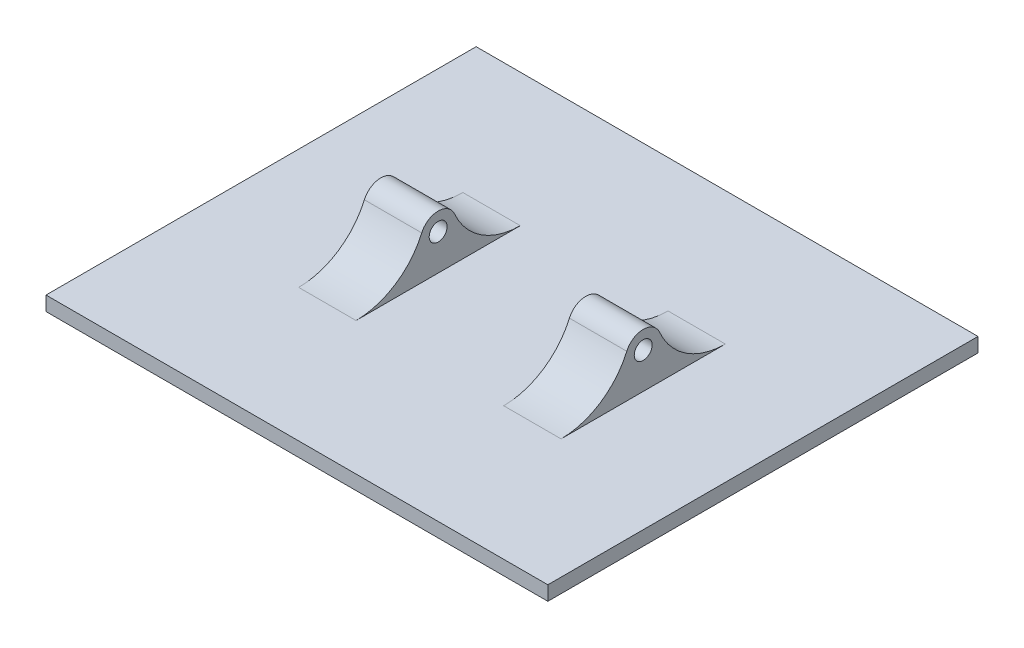
SolidWorks part; units mm, degrees
ref_plane "Front" through (0, 0, 0) normal (0, 0, 1) x (1, 0, 0)
ref_plane "Top" through (0, 0, 0) normal (0, 1, 0) x (1, 0, 0)
ref_plane "Right" through (0, 0, 0) normal (1, 0, 0) x (0, 0, -1)
sketch "Sketch1" plane through (0, 0, 0) normal (0, 0, 1) x (1, 0, 0)
  line L1 (0, 0) -> (20, 0)
  line L2 (0, 0) -> (0, 60)
  line L3 (0, 60) -> (20, 60)
  line L4 (20, 0) -> (20, 60)
  dimension "D1" = 60
  dimension "D2" = 20
extrude "Boss-Extrude1" add sketch "Sketch1" along normal blind 5
sketch "Sketch2" plane through (20, 0, 0) normal (1, 0, 0) x (0, 0, -1)
  line L0 (-5, 60) -> (0, 60) construction
  circle A0 centre (-2.5, 60) radius 2.5
  circle A1 centre (-2.5, 60) radius 1.25
  dimension "D1" = 2.5
extrude "Boss-Extrude2" add sketch "Sketch2" against normal up to surface (20 mm away) up to face at (0, 30, 2.5)
sketch "Sketch3" plane through (0, 0, 0) normal (-1, 0, 0) x (0, 0, 1)
  line L0 (3.75, 60) -> (1.25, 60) construction
  circle A0 centre (2.5, 60) radius 1.25
extrude "Cut-Extrude1" cut sketch "Sketch3" against normal blind 29
sketch "Sketch4" plane through (0, 0, 0) normal (-1, 0, 0) x (0, 0, 1)
  line L0 (5, 0) -> (0, 0) construction
  circle A0 centre (2.5, 0) radius 2.5
  circle A1 centre (2.5, 0) radius 1.25
  dimension "D1" = 2.5
extrude "Boss-Extrude3" add sketch "Sketch4" against normal up to surface (20 mm away) up to face at (20, 30.625, 2.5)
sketch "Sketch5" plane through (20, 0, 0) normal (1, 0, 0) x (0, 0, -1)
  line L0 (-3.75, 0) -> (-1.25, 0) construction
  circle A0 centre (-2.5, 0) radius 1.25
extrude "Cut-Extrude2" cut sketch "Sketch5" against normal blind 29
sketch "Sketch7" plane through (0, 0, 0) normal (-1, 0, 0) x (0, 0, 1)
  line L0 (0, -5) -> (-27.5, -5)
  line L2 (0, 0) -> (0, -5)
  line L4 (5, 0) -> (5, -5)
  line L5 (5, -5) -> (32.5, -5)
  line L6 (32.5, -5) -> (5, -5)
  line L7 (32.5, -5) -> (32.5, -7)
  line L8 (32.5, -5) -> (32.5, -7)
  line L9 (32.5, -7) -> (-27.5, -7)
  line L10 (-27.5, -5) -> (-27.5, -7)
  circle A0 centre (2.5, 0) radius 1.25
  arc A1 (5, 0) -> (0, 0) centre (2.5, 0) ccw
  point P13 (2.5, -7)
  point P14 (0, 0)
  arc M8 (0, 0) -> (5, 0) centre (2.5, 0) ccw
  circle M12 centre (2.5, 0) radius 1.25
  dimension "D1" = 5
  dimension "D2" = 2
  dimension "D3" = 60
extrude "Boss-Extrude4" add sketch "Sketch7" along normal blind 70 contours L0 L10 L9 L7 L5 L4 L2 M8 | A1 M8 M12 region at (0, -5.7114, 2.5) region at (0, 2.4293, 2.5)
sketch "Sketch8" plane through (0, -5, 0) normal (0, 1, 0) x (1, 0, 0)
  line L1 (-24.7, -10.7291) -> (-45.3, -10.7291)
  line L2 (-24.7, -10.7291) -> (-24.7, 7.5271)
  line L3 (-24.7, 7.5271) -> (-45.3, 7.5271)
  line L4 (-45.3, -10.7291) -> (-45.3, 7.5271)
  line L5 (-70, -32.5) -> (0, -32.5) construction
  line L6 (0, -5) -> (0, -32.5) construction
  line L7 (0, -16.9234) -> (-16.7, -16.9234)
  line L8 (0, -16.9234) -> (0, 11.5453)
  line L9 (0, 11.5453) -> (-16.7, 11.5453)
  line L10 (-16.7, -16.9234) -> (-16.7, 11.5453)
  line L11 (-70, -5) -> (-70, -32.5) construction
  line L12 (-70, -16.9234) -> (-53.3, -16.9234)
  line L13 (-70, -16.9234) -> (-70, 9.8234)
  line L14 (-70, 9.8234) -> (-53.3, 9.8234)
  line L15 (-53.3, -16.9234) -> (-53.3, 9.8234)
  point P4 (-35, -10.7291)
  point P7 (-35, -32.5)
  dimension "D1" = 20.6
  dimension "D2" = 8
  dimension "D3" = 8
extrude "Cut-Extrude4" cut sketch "Sketch8" along normal blind 84
sketch "Sketch9" plane through (-16.7, 0, 0) normal (1, 0, 0) x (0, 0, -1)
  line L0 (27.5, -5) -> (-32.5, -5) construction
  line L1 (-26.342, -5) -> (19.5452, -5)
  line L2 (-26.342, -5) -> (-26.342, 64.4459)
  line L3 (-26.342, 64.4459) -> (19.5452, 64.4459)
  line L4 (19.5452, -5) -> (19.5452, 64.4459)
extrude "Cut-Extrude5" cut sketch "Sketch9" along normal blind 115
fillet "Fillet1" radius 10 4 edges at (-20.7, -5, 5) (-49.3, -5, 5) (-49.3, -5, 0) (-20.7, -5, 0)
